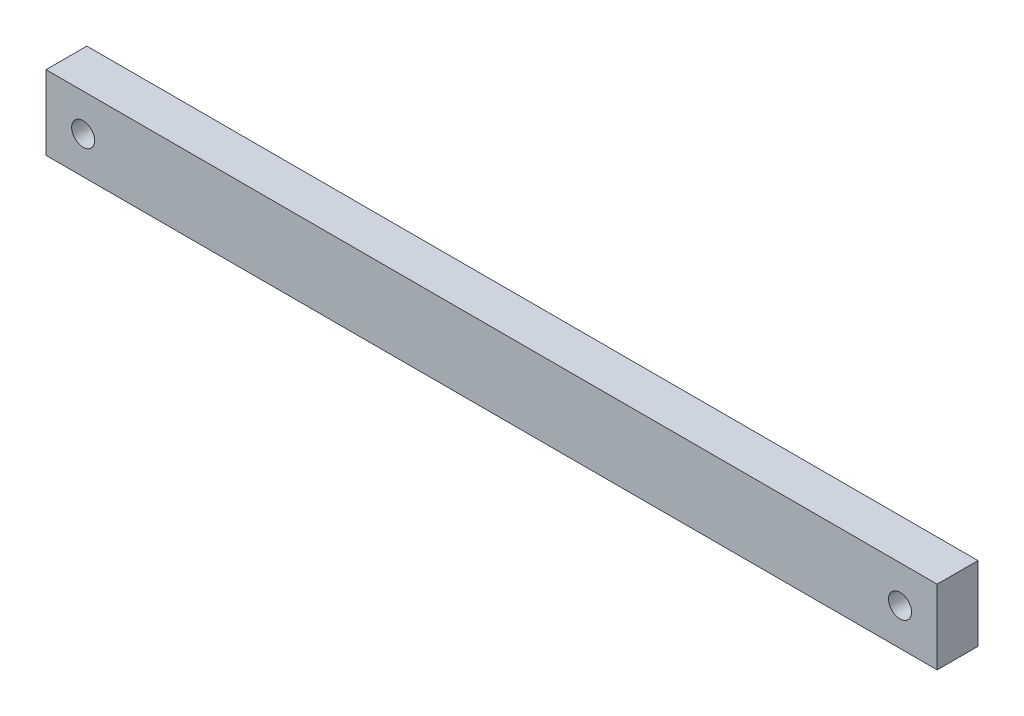
SolidWorks part; units mm, degrees
material "ﾁｰｸ材"
ref_plane "正面" through (0, 0, 0) normal (0, 0, 1) x (1, 0, 0)
ref_plane "平面" through (0, 0, 0) normal (0, 1, 0) x (1, 0, 0)
ref_plane "右側面" through (0, 0, 0) normal (1, 0, 0) x (0, 0, -1)
sketch "ｽｹｯﾁ1" plane through (0, 0, 0) normal (0, 0, 1) x (1, 0, 0)
  line L1 (60, 5) -> (-60, 5)
  line L2 (60, 5) -> (60, -5)
  line L3 (60, -5) -> (-60, -5)
  line L4 (-60, 5) -> (-60, -5)
  line L5 (60, 5) -> (-60, -5) construction
  line L6 (60, -5) -> (-60, 5) construction
  point P0 (0, 0)
  dimension "D1" = 10
  dimension "D2" = 120
extrude "ﾎﾞｽ - 押し出し1" add sketch "ｽｹｯﾁ1" along normal blind 5.5
sketch "ｽｹｯﾁ2" plane through (0, 0, 5.5) normal (0, 0, 1) x (1, 0, 0)
  line L0 (-60, 5) -> (-60, -5) construction
  line L1 (60, -5) -> (60, 5) construction
  circle A0 centre (-55, 0) radius 1.55
  circle A1 centre (55, 0) radius 1.55
  point P8 (-55, 5.6548)
  dimension "D1" = 3.1
  dimension "D2" = 5
  dimension "D3" = 5
extrude "ｶｯﾄ - 押し出し1" cut sketch "ｽｹｯﾁ2" against normal through all
